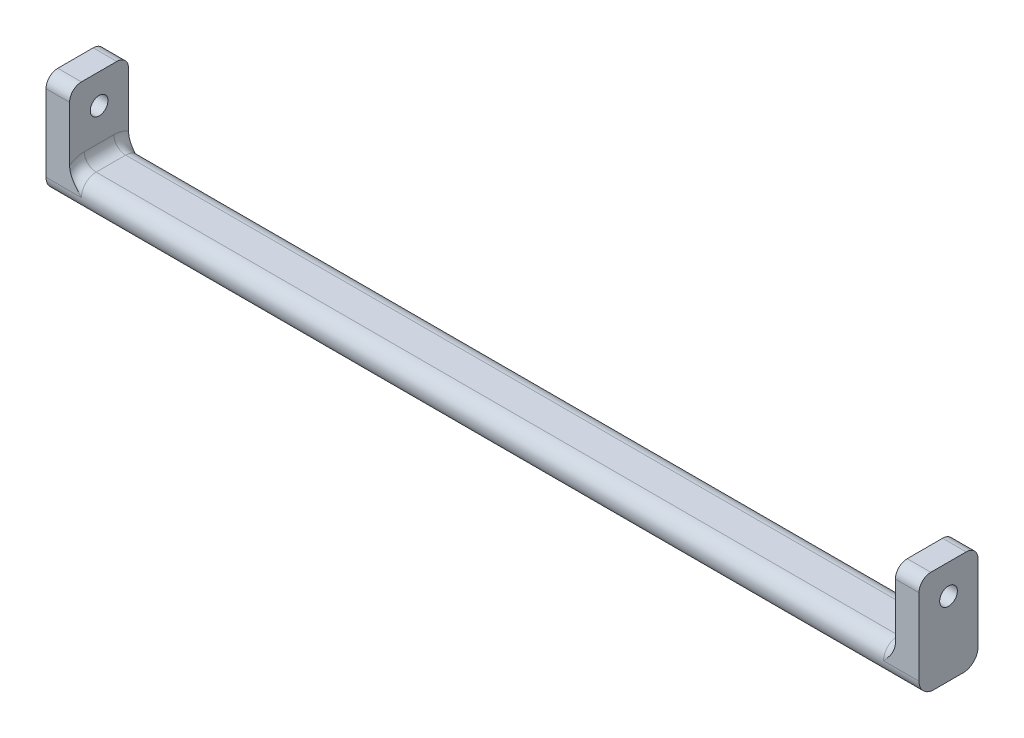
SolidWorks part; units mm, degrees
ref_plane "Front Plane" through (0, 0, 0) normal (0, 0, 1) x (1, 0, 0)
ref_plane "Top Plane" through (0, 0, 0) normal (0, 1, 0) x (1, 0, 0)
ref_plane "Right Plane" through (0, 0, 0) normal (1, 0, 0) x (0, 0, -1)
sketch "Sketch1" plane through (0, 0, 0) normal (1, 0, 0) x (0, 0, -1)
  line L0 (-2.5, 0) -> (2.5, 0) construction
  line L1 (-2.5, 2.5) -> (2.5, 2.5)
  line L2 (-2.5, -2.5) -> (2.5, -2.5)
  circle A0 centre (0, 0) radius 1.5
  circle A1 centre (0, 0) radius 2.5 construction
  arc A2 (-2.5, 2.5) -> (-2.5, -2.5) centre (-2.5, 0) ccw
  arc A3 (2.5, -2.5) -> (2.5, 2.5) centre (2.5, 0) ccw
  point P7 (0, 0)
  dimension "D1" = 3
  dimension "D3" = 5
  dimension "D2" = 1
extrude "Boss-Extrude1" add sketch "Sketch1" along normal mid plane 148 contours A0 | A1 A0 region at (0, 2.3882, 0) region at (0, 0, 0)
sketch "Sketch3" plane through (74, 0, 0) normal (1, 0, 0) x (0, 0, -1)
  line L0 (-2.5, -2.5) -> (2.5, -2.5) construction
  line L1 (-2.5, -2.5) -> (2.5, -2.5)
  line L2 (-5, 0) -> (-5, 13)
  line L3 (-3, 15) -> (3, 15)
  line L4 (5, 0) -> (5, 13)
  line L5 (0, 6.875) -> (0, -6.875) construction
  arc A0 (-2.5, 2.5) -> (-2.5, -2.5) centre (-2.5, 0) ccw construction
  arc A1 (2.5, -2.5) -> (2.5, 2.5) centre (2.5, 0) ccw construction
  arc A2 (2.5, -2.5) -> (5, 0) centre (2.5, 0) ccw
  arc A3 (-2.5, -2.5) -> (-5, 0) centre (-2.5, 0) cw
  arc A4 (3, 15) -> (5, 13) centre (3, 13) cw
  arc A5 (-5, 13) -> (-3, 15) centre (-3, 13) cw
  point P23 (-5, 15)
  dimension "D2" = 2
  dimension "D1" = 15
extrude "Boss-Extrude2" add sketch "Sketch3" against normal blind 4
fillet "Fillet1" radius 2 3 edges at (70, 1.7678, 4.2678) (70, 2.5, 0) (70, 1.7678, -4.2678)
sketch "Sketch2" plane through (74, 0, 0) normal (1, 0, 0) x (0, 0, -1)
  line L0 (3, 15) -> (-3, 15) construction
  circle A0 centre (0, 10) radius 1.5
  dimension "D1" = 3
  dimension "D2" = 5
extrude "Cut-Extrude1" cut sketch "Sketch2" against normal blind 5
mirror "Mirror1" about plane through (0, 0, 0) normal (1, 0, 0) of "Boss-Extrude2", "Fillet1", "Cut-Extrude1"
